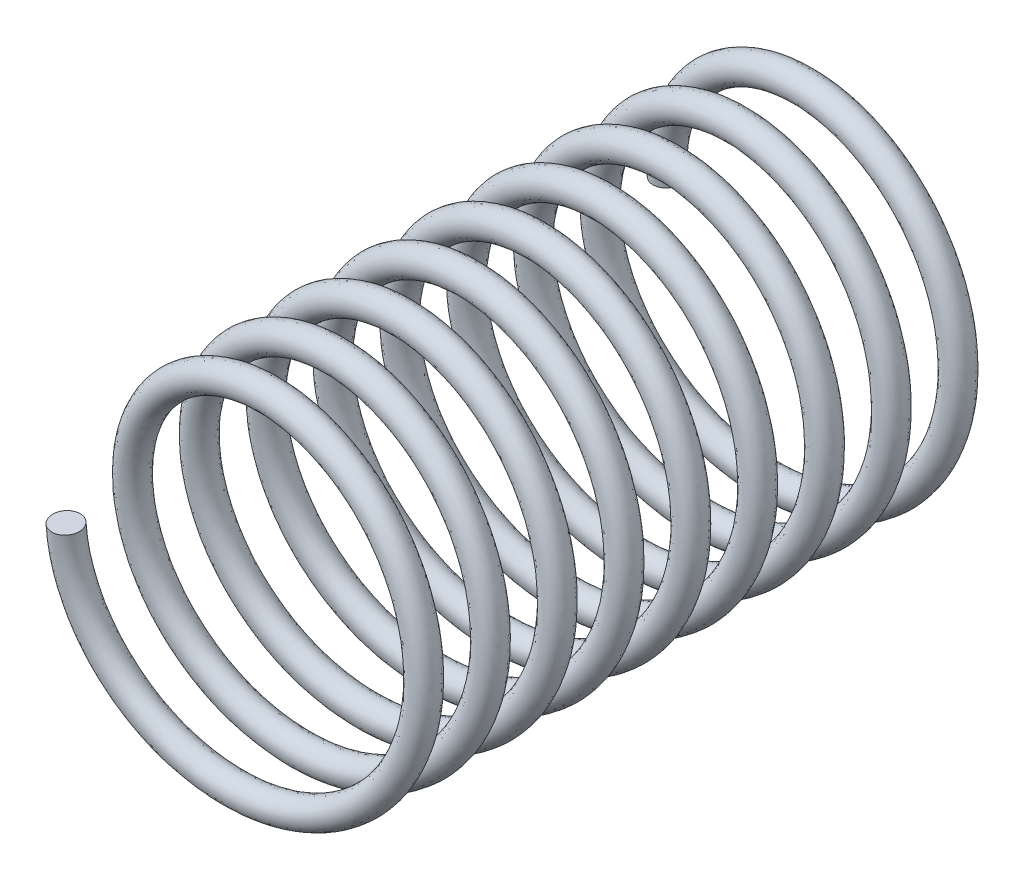
SolidWorks part; units mm, degrees
ref_plane "前视基准面" through (0, 0, 0) normal (0, 0, 1) x (1, 0, 0)
ref_plane "上视基准面" through (0, 0, 0) normal (0, 1, 0) x (1, 0, 0)
ref_plane "右视基准面" through (0, 0, 0) normal (1, 0, 0) x (0, 0, -1)
sketch "草图1" plane through (0, 0, 0) normal (0, 0, 1) x (1, 0, 0)
  circle A0 centre (-4.7585, 12.5795) radius 8
  dimension "D1" = 16
curve "螺旋线/涡状线1" pitch 3.3 height 29.7 turns 9
ref_plane "基准面1" through (-12.7585, 12.5795, 0) normal (0, 0.9979, 0.0655) x (1, 0, 0)
sketch "草图2" plane through (-12.7585, 12.5795, 0) normal (0, 0.9979, 0.0655) x (1, 0, 0)
  circle A0 centre (0, 0) radius 0.7
  dimension "D1" = 1.4
sweep "扫描1" add profiles "草图2" path "螺旋线/涡状线1"
ref_plane "基准面2" through (0, 0, 30) normal (0, 0, 1) x (1, 0, 0)
ref_plane "基准面3" through (0, 0, -2.5) normal (0, 0, 1) x (1, 0, 0)
sketch "草图6" plane through (0, 0, -2.5) normal (0, 0, 1) x (1, 0, 0)
  circle A0 centre (-4.7585, 12.5795) radius 5 construction
  dimension "D1" = 10
